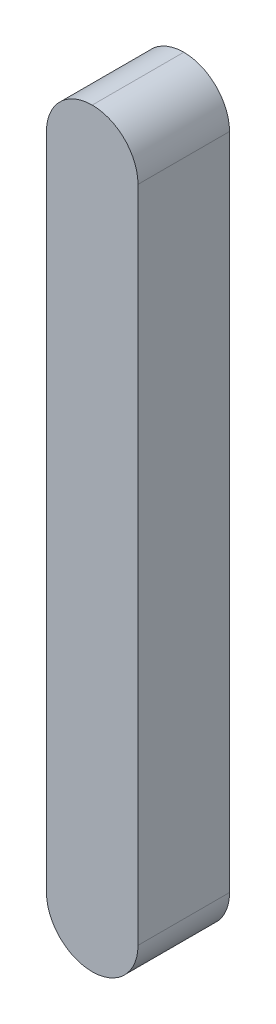
SolidWorks part; units mm, degrees
ref_plane "前视基准面" through (0, 0, 0) normal (0, 0, 1) x (1, 0, 0)
ref_plane "上视基准面" through (0, 0, 0) normal (0, 1, 0) x (1, 0, 0)
ref_plane "右视基准面" through (0, 0, 0) normal (1, 0, 0) x (0, 0, -1)
sketch "Sketch1" plane through (0, 0, 0) normal (0, 1, 0) x (1, 0, 0)
  line L1 (-2.5, 2.5) -> (2.5, 2.5)
  line L2 (-2.5, 2.5) -> (-2.5, -2.5)
  line L3 (-2.5, -2.5) -> (2.5, -2.5)
  line L4 (2.5, 2.5) -> (2.5, -2.5)
  line L5 (-2.5, 2.5) -> (2.5, -2.5) construction
  line L6 (-2.5, -2.5) -> (2.5, 2.5) construction
  point P0 (0, 0)
  dimension "D1" = 5
  dimension "D2" = 5
extrude "Boss-Extrude1" add sketch "Sketch1" along normal mid plane 41
fillet "Fillet1" radius 2.5 4 edges at (-2.5, -20.5, 0) (2.5, -20.5, 0) (2.5, 20.5, 0) (-2.5, 20.5, 0)
